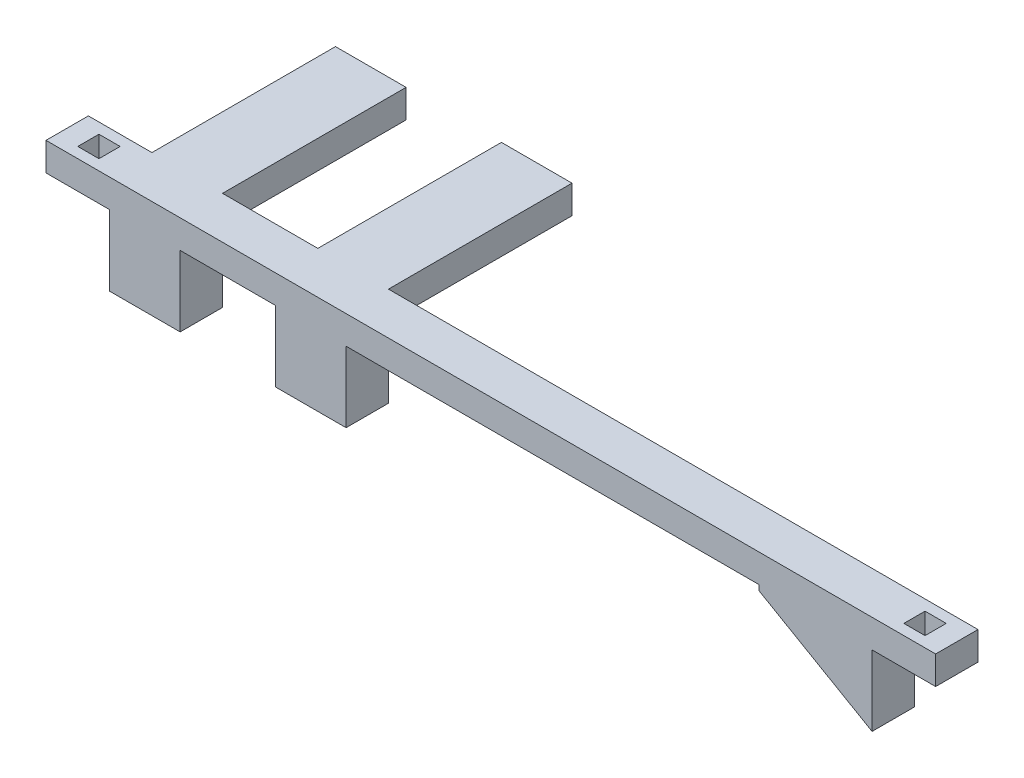
SolidWorks part; units mm, degrees
ref_plane "Front Plane" through (0, 0, 0) normal (0, 0, 1) x (1, 0, 0)
ref_plane "Top Plane" through (0, 0, 0) normal (0, 1, 0) x (1, 0, 0)
ref_plane "Right Plane" through (0, 0, 0) normal (1, 0, 0) x (0, 0, -1)
sketch "Sketch1" plane through (0, 0, 0) normal (0, 1, 0) x (1, 0, 0)
  line L1 (0, 0) -> (126, 0)
  line L2 (0, 0) -> (0, 6)
  line L3 (0, 6) -> (126, 6)
  line L4 (126, 0) -> (126, 6)
  dimension "D1" = 126
  dimension "D2" = 6
extrude "Boss-Extrude1" add sketch "Sketch1" along normal blind 4
sketch "Sketch2" plane through (0, 4, 0) normal (0, 1, 0) x (1, 0, 0)
  line L0 (126, 6) -> (0, 6) construction
  line L1 (120, 4.5) -> (123, 4.5)
  line L2 (120, 4.5) -> (120, 1.5)
  line L3 (120, 1.5) -> (123, 1.5)
  line L4 (123, 4.5) -> (123, 1.5)
  line L5 (126, 0) -> (126, 6) construction
  line L6 (0, 6) -> (0, 0) construction
  line L7 (3, 4.5) -> (6, 4.5)
  line L8 (3, 4.5) -> (3, 1.5)
  line L9 (3, 1.5) -> (6, 1.5)
  line L10 (6, 4.5) -> (6, 1.5)
  dimension "D1" = 3
  dimension "D2" = 3
  dimension "D3" = 1.5
  dimension "D4" = 3
  dimension "D5" = 3
  dimension "D6" = 3
  dimension "D7" = 1.5
  dimension "D8" = 3
extrude "Cut-Extrude1" cut sketch "Sketch2" against normal blind 4
sketch "Sketch3" plane through (0, 0, 0) normal (0, 1, 0) x (1, 0, 0)
  line L0 (126, 6) -> (0, 6) construction
  line L1 (9, 6) -> (19, 6)
  line L2 (9, 6) -> (9, 0)
  line L3 (9, 0) -> (19, 0)
  line L4 (19, 6) -> (19, 0)
  line L5 (0, 0) -> (126, 0) construction
  line L6 (6, 1.5) -> (6, 4.5) construction
  line L7 (120, 4.5) -> (120, 1.5) construction
  line L8 (101, 6) -> (117, 6)
  line L9 (101, 6) -> (101, 0)
  line L10 (101, 0) -> (117, 0)
  line L11 (117, 6) -> (117, 0)
  line L13 (32.5, 6) -> (42.5, 6)
  line L14 (32.5, 6) -> (32.5, 0)
  line L15 (32.5, 0) -> (42.5, 0)
  line L16 (42.5, 6) -> (42.5, 0)
  dimension "D1" = 10
  dimension "D2" = 3
  dimension "D3" = 16
  dimension "D4" = 3
  dimension "D5" = 10
  dimension "D6" = 23.5
extrude "Boss-Extrude2" add sketch "Sketch3" against normal blind 10
chamfer "Chamfer1" distance 16 angle 30 1 edges at (101, -10, -3) first distance on face at (109, -10, -3)
sketch "Sketch4" plane through (0, 0, -6) normal (0, 0, -1) x (-1, 0, 0)
  line L0 (-126, 4) -> (0, 4) construction
  line L1 (-19, 0) -> (-9, 0)
  line L2 (-19, 0) -> (-19, 4)
  line L3 (-19, 4) -> (-9, 4)
  line L4 (-9, 0) -> (-9, 4)
  line L6 (-42.5, 0) -> (-32.5, 0)
  line L7 (-42.5, 0) -> (-42.5, 4)
  line L8 (-42.5, 4) -> (-32.5, 4)
  line L9 (-32.5, 0) -> (-32.5, 4)
  dimension "D1" = 10
  dimension "D2" = 10
extrude "Boss-Extrude3" add sketch "Sketch4" along normal blind 26
